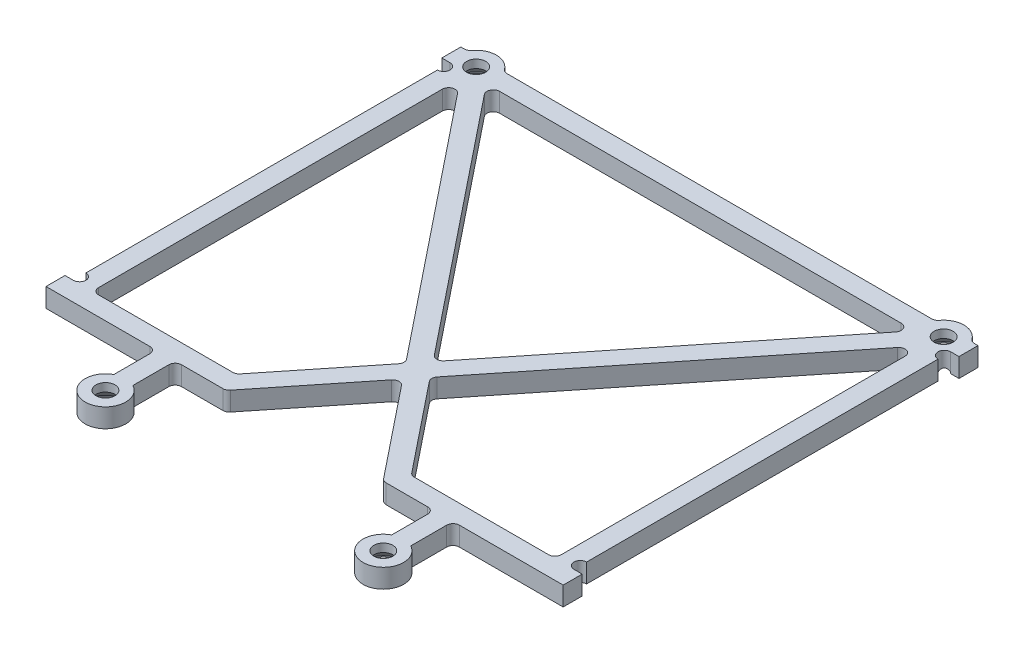
SolidWorks part; units mm, degrees
ref_plane "Front Plane" through (0, 0, 0) normal (0, 0, 1) x (1, 0, 0)
ref_plane "Top Plane" through (0, 0, 0) normal (0, 1, 0) x (1, 0, 0)
ref_plane "Right Plane" through (0, 0, 0) normal (1, 0, 0) x (0, 0, -1)
sketch "Sketch1" plane through (0, 0, 0) normal (0, 1, 0) x (1, 0, 0)
  line L0 (-36.88, 36.725) -> (36.88, 36.725) construction
  line L1 (-39.5, -24.225) -> (-39.5, 35.225)
  line L2 (21.92, -36.725) -> (-21.92, -36.725) construction
  line L3 (-36.5, -24.225) -> (-36.5, 35.225)
  line L4 (0, -40.095) -> (0, -36.725) construction
  line L5 (0, 36.725) -> (0, -36.725) construction
  line L6 (40.8, 38.225) -> (-40.8, 38.225)
  line L9 (40.8, 38.225) -> (40.8, 35.225)
  line L17 (40.8, 35.225) -> (-40.8, 35.225)
  line L18 (-40.8, 38.225) -> (-40.8, 35.225)
  line L23 (40.8, 38.225) -> (-40.8, 35.225) construction
  line L24 (40.8, 35.225) -> (-40.8, 38.225) construction
  line L60 (-21.92, -36.725) -> (36.88, 36.725) construction
  line L62 (21.92, -36.725) -> (-36.88, 36.725) construction
  line L66 (23.091, -35.7876) -> (-35.709, 37.6624)
  line L67 (20.749, -37.6624) -> (-38.051, 35.7876)
  line L68 (-20.749, -37.6624) -> (38.051, 35.7876)
  line L69 (-23.091, -35.7876) -> (35.709, 37.6624)
  line L71 (-36.5, 5.5) -> (-39.5, 5.5) construction
  line L73 (36.5, -24.225) -> (36.5, 35.225)
  line L74 (39.5, -24.225) -> (39.5, 35.225)
  line L75 (-36.5, -24.225) -> (-36.5, -27.225) construction
  line L76 (-40.8, -24.225) -> (40.8, -24.225)
  line L77 (-40.8, -24.225) -> (-40.8, -27.225)
  line L78 (-40.8, -27.225) -> (40.8, -27.225)
  line L79 (40.8, -24.225) -> (40.8, -27.225)
  line L80 (-40.8, -24.225) -> (40.8, -27.225) construction
  line L81 (-40.8, -27.225) -> (40.8, -24.225) construction
  line L82 (-21.92, -36.725) -> (-21.92, -27.225) construction
  line L84 (-23.42, -27.225) -> (-20.42, -27.225)
  line L85 (-23.42, -27.225) -> (-23.42, -33.8983)
  line L86 (-23.42, -33.8983) -> (-20.42, -33.8983)
  line L87 (-20.42, -27.225) -> (-20.42, -33.8983)
  line L88 (-23.42, -27.225) -> (-20.42, -33.8983) construction
  line L89 (-23.42, -33.8983) -> (-20.42, -27.225) construction
  line L90 (20.42, -27.225) -> (20.42, -33.8983)
  line L91 (23.42, -27.225) -> (23.42, -33.8983)
  circle A0 centre (21.92, -36.725) radius 1.5
  circle A1 centre (-21.92, -36.725) radius 1.5
  circle A2 centre (-36.88, 36.725) radius 1.5
  circle A3 centre (36.88, 36.725) radius 1.5
  circle A4 centre (-36.88, 36.725) radius 3.2
  circle A5 centre (-21.92, -36.725) radius 3.2
  circle A6 centre (21.92, -36.725) radius 3.2
  circle A7 centre (36.88, 36.725) radius 3.2
  circle A8 centre (0, -40.095) radius 16
  circle A9 centre (-39.5, 34.225) radius 1
  circle A10 centre (39.5, 34.225) radius 1
  circle A11 centre (-39.5, -23.225) radius 1
  circle A12 centre (39.5, -23.225) radius 1
  point P10 (0, 0)
  point P18 (-21.92, -30.5617)
  point P58 (0, -25.725)
  point P60 (0, 0)
  dimension "D4" = 3
  dimension "D5" = 6.4
  dimension "D6" = 32
  dimension "D9" = 3
  dimension "D17" = 2
  dimension "D1" = 74.958
  dimension "D2" = 43.84
  dimension "D3" = 73.76
  dimension "D7" = 3.37
  dimension "D8" = 81.6
  dimension "D10" = 79
  dimension "D13" = 1.5
  dimension "D14" = 1.5
  dimension "D15" = 1.5
  dimension "D16" = 1.5
  dimension "D18" = 11
extrude "Shape" add sketch "Sketch1" along normal blind 3 contours L9 | L9 | A4 L6 L18 L17 | L6 A4 | L6 A4 L17 L67 A2 | L66 A4 L6 A2 | L17 A4 L66 A2 | L67 A4 L17 L3 | L67 L3 L17 | A2 L67 L17 | A9 A4 L3 L67 L17 | A11 L76 L3 A4 A9 L1 | A4 L67 L69 L66 L17 | A4 L17 L66 | A7 L6 A4 L66 L17 L69 | L6 A7 L69 A3 | L6 A7 | L17 A7 L6 A3 L68 | A7 L17 L9 L6 | A7 A10 L17 L68 L73 | A3 L17 L68 | L69 A7 L17 A3 | L17 A7 L68 L73 | L73 L68 L17 | A7 L69 L17 | A7 L17 L69 L66 L68 | L76 A12 L74 A10 A7 L73 | L69 L67 L68 L66 | L69 L76 L68 L67 | L67 L76 L66 L68 | L77 L78 L69 L76 | A5 L69 L87 L78 L85 | A5 L87 L69 | L86 A5 L69 | L69 A5 L86 | L86 A5 L68 A1 L69 | L68 A5 L86 L69 A1 | L69 L78 L68 L76 | L67 L78 L66 L76 | L79 L76 L66 L78 | A6 L91 L78 L90 L66 | A6 L66 L90 | A6 L66 A0 L67 | L66 A6 L67 A0 region at (-27.9084, 0, 25.7017) region at (-37.9894, 0, -4.9296) region at (-37.7315, 0, -34.3772) region at (-13.114, 0, 25.725) region at (-6.4791, 0, 17.3668) region at (-21.9608, 0, 30.3398) region at (-36.8669, 0, -34.7667) region at (-35.5453, 0, -34.5717) region at (-17.9573, 0, -13.0823) region at (0, 0, 9.3436) region at (-39.0008, 0, -36.743) region at (-40.3721, 0, -36.725) region at (-22.2364, 0, 33.7343) region at (-22.4993, 0, 33.9863) region at (-35.0617, 0, -35.8515) region at (-37.5447, 0, -35.3415) region at (-33.9168, 0, -35.3014) region at (-20.7161, 0, 33.2949) region at (6.4791, 0, 17.3668) region at (17.9573, 0, -13.0823) region at (-36.88, 0, -38.9233) region at (-20.5884, 0, 35.1329) region at (-21.0809, 0, 33.7851) region at (0, 0, -36.7255) region at (-34.6096, 0, -37.2433) region at (13.114, 0, 25.725) region at (33.9168, 0, -35.3014) region at (27.9084, 0, 25.7017) region at (35.5453, 0, -34.5717) region at (35.0617, 0, -35.8515) region at (34.6096, 0, -37.2433) region at (36.88, 0, -38.9233) region at (20.6063, 0, 35.084) region at (19.7951, 0, 36.6157) region at (37.9894, 0, -4.9296) region at (36.8669, 0, -34.7667) region at (37.7315, 0, -34.3772) region at (39.0008, 0, -36.743) region at (40.3721, 0, -36.725) region at (20.7161, 0, 33.2949) region at (21.9608, 0, 30.3398) region at (37.5447, 0, -35.3415)
fillet "Mill fillets" radius 1 22 edges at (39.7067, 1.5, -38.225) (34.0533, 1.5, -38.225) (-39.7067, 1.5, -38.225) (-34.0533, 1.5, -38.225) (1.9214, 1.5, 9.3436) (-1.9214, 1.5, 9.3436) (33.7577, 1.5, -35.225) (-33.7577, 1.5, -35.225) (0, 1.5, 11.7438) (-36.5, 1.5, 24.225) (13.8346, 1.5, 24.225) (36.5, 1.5, 24.225) (-13.8346, 1.5, 24.225) (36.5, 1.5, -33.8501) (-36.5, 1.5, -33.8501) (0, 1.5, 6.9435) (-23.42, 1.5, 27.225) (20.42, 1.5, 27.225) (23.42, 1.5, 27.225) (-20.42, 1.5, 27.225) (12.3934, 1.5, 27.225) (-12.3934, 1.5, 27.225)
hole_wizard "M3 countersunks" positions "Sketch2" profile "Sketch3" countersink size "M3" standard "ANSI Metric" end condition through all
sketch "Sketch2" plane through (0, 0, 0) normal (0, -1, 0) x (-1, 0, 0)
  point P0 (21.92, -36.725)
  point P3 (-21.92, -36.725)
  point P6 (-36.88, 36.725)
  point P9 (36.88, 36.725)
sketch "Sketch3" plane through (-21.92, 0, 36.725) normal (1, 0, 0) x (0, 0, -1)
  line L0 (0, 0) -> (0, 3)
  line L1 (0, 3) -> (1.5, 3)
  line L2 (1.5, 3) -> (1.5, 1.7)
  line L3 (1.5, 1.7) -> (3, 0.2)
  line L4 (3, 0.2) -> (3, 0)
  line L6 (3, 0) -> (0, 0)
  line L7 (-1.5, 1.7) -> (-3, 0.2) construction
  line L11 (0, -6.35) -> (0, 107.95) construction
  dimension "Thru Hole Dia." = 3
  dimension "Thru Hole Depth" = 3
  dimension "C'Sink Dia." = 6
  dimension "C'Sink Angle" = 90
  dimension "Head Clearance" = 0.2
